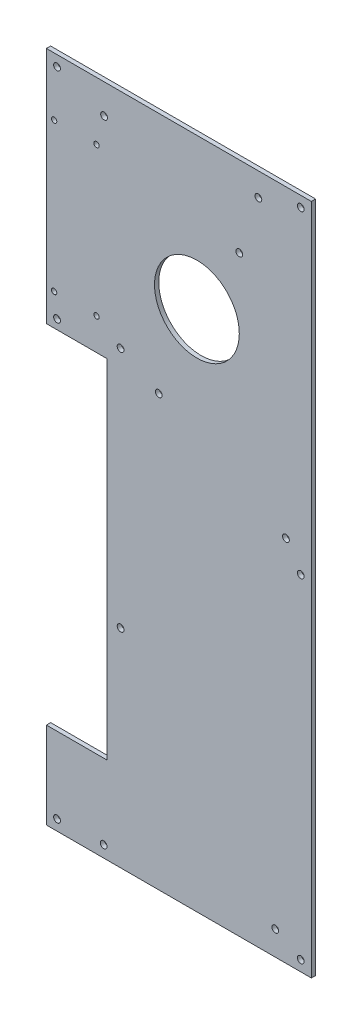
SolidWorks part; units mm, degrees
ref_plane "Front Plane" through (0, 0, 0) normal (1, 0, 0) x (0, 1, 0)
ref_plane "Top Plane" through (0, 0, 0) normal (0, 0, 1) x (0, 1, 0)
ref_plane "Right Plane" through (0, 0, 0) normal (0, 1, 0) x (-1, 0, 0)
sketch "Sketch1" plane through (0, 0, 0) normal (0, 0, 1) x (0, 1, 0)
  line L0 (-57.15, 6.35) -> (-57.15, 35)
  line L1 (-98, 6.35) -> (219.3, 6.35)
  line L2 (-98, 6.35) -> (-98, -90)
  line L3 (-98, -90) -> (219.3, -90)
  line L4 (219.3, 6.35) -> (219.3, -90)
  line L5 (-57.15, 35) -> (-98, 35)
  line L6 (-98, 35) -> (-98, 6.35)
  line L7 (196.85, 6.35) -> (196.85, 35)
  line L8 (196.85, 35) -> (219.3, 35)
  line L9 (219.3, 35) -> (219.3, 6.35)
  line L10 (196.85, 35) -> (106.85, 35)
  line L11 (121.85, 31.35) -> (191.85, 31.35) construction
  line L12 (121.85, 31.35) -> (121.85, 11.35) construction
  line L13 (121.85, 11.35) -> (191.85, 11.35) construction
  line L14 (191.85, 31.35) -> (191.85, 11.35) construction
  line L15 (106.85, 35) -> (106.85, 6.35)
  circle A0 centre (-86.5, -73) radius 1.6
  circle A1 centre (-92.5, 8) radius 1.6
  circle A2 centre (0, 0) radius 1.6
  circle A3 centre (114.3, 0) radius 1.6
  circle A4 centre (104.8, -18) radius 1.6
  circle A5 centre (181.3, -56) radius 1.6
  circle A6 centre (208.3, -65) radius 1.6
  circle A7 centre (205.3, 7.8) radius 1.6
  circle A8 centre (75.7, -78) radius 1.6
  circle A18 centre (148.3, -36) radius 20
  circle A19 centre (-93, 30) radius 1.6
  circle A20 centre (-93, -85) radius 1.6
  circle A21 centre (214.3, -85) radius 1.6
  circle A22 centre (214.3, 30) radius 1.6
  circle A23 centre (121.85, 31.35) radius 1.25
  circle A24 centre (121.85, 11.35) radius 1.25
  circle A25 centre (191.85, 11.35) radius 1.25
  circle A26 centre (191.85, 31.35) radius 1.25
  circle A27 centre (111.3, 30) radius 1.6
  circle A28 centre (64.3, -85) radius 1.6
  dimension "D1" = 3.2
  dimension "D13" = 78
  dimension "D23" = 3.2
  dimension "D26" = 34
  dimension "D27" = 40
  dimension "D29" = 5
  dimension "D34" = 2.5
  dimension "D38" = 103
  dimension "D39" = 150
  dimension "D2" = 114.3
  dimension "D3" = 8
  dimension "D4" = 92.5
  dimension "D5" = 73
  dimension "D6" = 86.5
  dimension "D7" = 98
  dimension "D8" = 105
  dimension "D9" = 91
  dimension "D10" = 7.8
  dimension "D11" = 94
  dimension "D12" = 65
  dimension "D14" = 38.6
  dimension "D15" = 9.5
  dimension "D16" = 18
  dimension "D17" = 67
  dimension "D18" = 56
  dimension "D19" = 90
  dimension "D20" = 6.35
  dimension "D21" = 57.15
  dimension "D22" = 35
  dimension "D24" = 5
  dimension "D25" = 82.55
  dimension "D28" = 36
  dimension "D30" = 5
  dimension "D31" = 5
  dimension "D32" = 20
  dimension "D33" = 70
  dimension "D35" = 5
  dimension "D36" = 5
  dimension "D37" = 15
extrude "Boss-Extrude1" add sketch "Sketch1" against normal blind 2 contours A7 L1 L2 L3 L4 A21 A20 A18 A8 A6 A5 A4 A3 A2 A0 | L5 L6 L1 L0 A19 A1 | A7 L1 L9 L8 L7 A22 | L10 L15 L1 L7 A26 A25 A24 A23 region at (-20.6983, -77.3635, 0) region at (42.0407, 56.833, 0) region at (-20.6404, 151.9394, 0) region at (-20.7174, 208.0302, 0)
